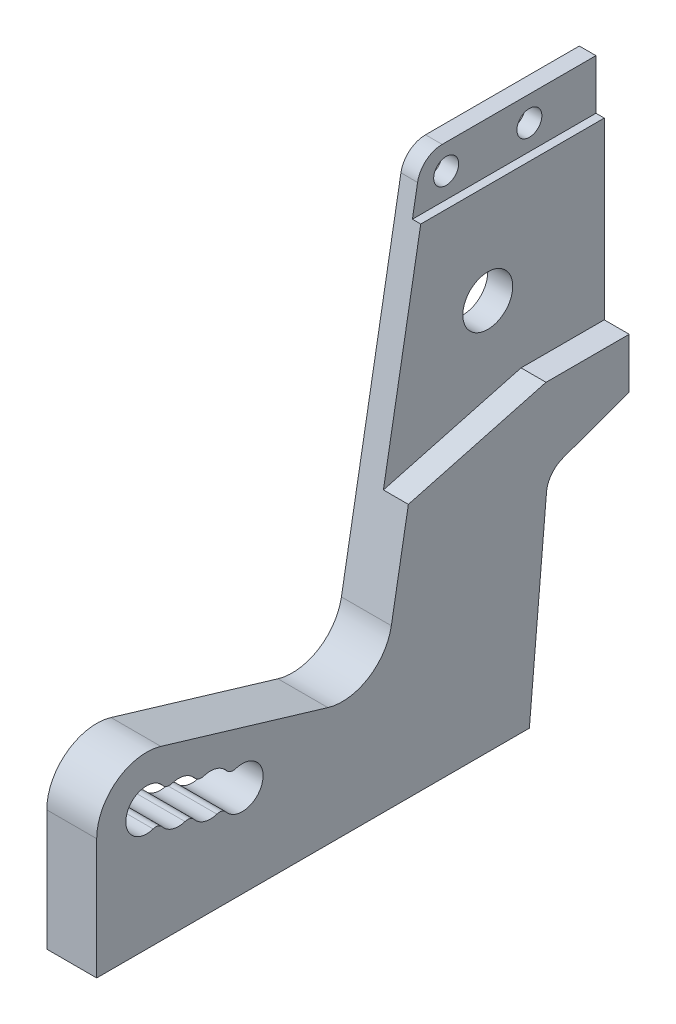
SolidWorks part; units mm, degrees
material "1060 Alloy"
ref_plane "Front Plane" through (0, 0, 0) normal (0, 0, 1) x (1, 0, 0)
ref_plane "Top Plane" through (0, 0, 0) normal (0, 1, 0) x (1, 0, 0)
ref_plane "Right Plane" through (0, 0, 0) normal (1, 0, 0) x (0, 0, -1)
sketch "Sketch1" plane through (0, 0, 0) normal (1, 0, 0) x (0, 0, -1)
  line L1 (0, 0) -> (64, 0)
  line L2 (0, 0) -> (0, 62)
  line L3 (0, 62) -> (64, 62)
  line L4 (64, 0) -> (64, 62)
  circle A0 centre (6, 14.5) radius 2.5
  circle A1 centre (50, 44) radius 3
  dimension "D1" = 6
  dimension "D2" = 5
  dimension "D3" = 14.5
  dimension "D4" = 6
  dimension "D5" = 44
  dimension "D6" = 50
  dimension "D7" = 64
  dimension "D8" = 62
extrude "Boss-Extrude1" add sketch "Sketch1" along normal blind 6
sketch "Sketch3" plane through (6, 0, 0) normal (1, 0, 0) x (0, 0, -1)
  line L57 (64, 0) -> (52, 0)
  line L58 (64, 0) -> (64, 29)
  line L59 (64, 29) -> (54.2259, 25.4425)
  line L60 (52, 0) -> (54.2259, 25.4425)
  dimension "D1" = 70
  dimension "D2" = 29
  dimension "D3" = 52
  dimension "D4" = 85
extrude "Cut-Extrude2" cut sketch "Sketch3" against normal up to next
fillet "Fillet2" radius 3 1 edges at (3, 25.4425, -54.2259)
hole_wizard "Tap Drill for M3 Tap1" positions "Sketch5" profile "Sketch4" hole size "M3" standard "ISO"
sketch "Sketch5" plane through (0, 0, 0) normal (0, -1, 0) x (-1, 0, 0)
  line L0 (0, 0) -> (0, 52) construction
  line L1 (-6, 0) -> (0, 0) construction
  point P0 (-3, 46)
  point P2 (-3, 10)
  dimension "D1" = 3
  dimension "D2" = 10
  dimension "D3" = 36
sketch "Sketch4" plane through (3, 0, -46) normal (1, 0, 0) x (0, 0, -1)
  line L0 (0, 0) -> (0, 9.7511)
  line L1 (0, 9.7511) -> (1.25, 9)
  line L2 (1.25, 9) -> (1.25, 0)
  line L5 (1.25, 0) -> (0, 0)
  line L10 (0, 9.7511) -> (-1.25, 9) construction
  line L11 (0, -6.35) -> (0, 107.95) construction
  dimension "Hole Dia." = 2.5
  dimension "Hole Depth" = 9
  dimension "Drill Angle" = 118
sketch "Sketch9" plane through (6, 0, 0) normal (1, 0, 0) x (0, 0, -1)
  line L0 (7.7183, 20.2487) -> (27.7834, 14.2513)
  line L1 (0, 0) -> (52, 0) construction
  line L19 (43, 62) -> (35.4106, 18.9581)
  line L21 (0, 62) -> (0, 0) construction
  line L22 (43, 62) -> (0, 62)
  line L23 (0, 62) -> (0, 14.5)
  line L24 (0, 62) -> (0, 0) construction
  line L25 (64, 62) -> (0, 62) construction
  arc A0 (35.4106, 18.9581) -> (27.7834, 14.2513) centre (29.5017, 20) cw
  arc A12 (0, 14.5) -> (7.7183, 20.2487) centre (6, 14.5) cw
  circle A16 centre (6, 14.5) radius 2.5 construction
  dimension "D1" = 43
  dimension "D2" = 80
  dimension "D3" = 20
extrude "Cut-Extrude3" cut sketch "Sketch9" against normal blind 8
sketch "Sketch13" plane through (6, 0, 0) normal (1, 0, 0) x (0, 0, -1)
  line L0 (64, 29) -> (64, 62) construction
  line L1 (54, 35) -> (64, 35)
  line L2 (64, 62) -> (43, 62) construction
  line L3 (64, 62) -> (43, 62)
  line L4 (64, 35) -> (64, 62)
  line L5 (35.4106, 18.9581) -> (43, 62) construction
  line L11 (43, 62) -> (37.4576, 30.5675)
  line L15 (37.4576, 30.5675) -> (54, 35)
  dimension "D1" = 10
  dimension "D2" = 65
  dimension "D3" = 27
extrude "Cut-Extrude4" cut sketch "Sketch13" against normal blind 3
fillet "Fillet3" radius 3 1 edges at (1.5, 62, -43)
sketch "Sketch14" plane through (3, 0, 0) normal (1, 0, 0) x (0, 0, -1)
  line L0 (64, 35) -> (64, 62) construction
  line L1 (64, 62) -> (45.5173, 62) construction
  circle A0 centre (56, 59) radius 1.5
  circle A1 centre (46, 59) radius 1.5
  dimension "D1" = 3
  dimension "D2" = 10
  dimension "D3" = 8
  dimension "D4" = 3
extrude "Cut-Extrude5" cut sketch "Sketch14" against normal up to next
sketch "Sketch15" plane through (0, 0, 0) normal (-1, 0, 0) x (0, 0, 1)
  line L0 (-6, 14.5) -> (-26.0652, 8.5026) construction
  line L1 (-27.7834, 14.2513) -> (-7.7183, 20.2487) construction
  circle A0 centre (-9.8325, 13.3545) radius 2.5
  circle A1 centre (-6, 14.5) radius 2.5 construction
  dimension "D1" = 4
extrude "Cut-Extrude6" cut sketch "Sketch15" against normal up to next
pattern_linear "LPattern3" count 3 spacing 4 along (0, -0.2864, -0.9581) of "Cut-Extrude6"
fillet "Fillet4" radius 1 6 edges at (3, 12.4901, -7.4867) (3, 11.3446, -11.3191) (3, 10.1991, -15.1516) (3, 13.0734, -16.0107) (3, 14.2189, -12.1783) (3, 15.3644, -8.3458)
sketch "Sketch16" plane through (3, 0, 0) normal (1, 0, 0) x (0, 0, -1)
  line L0 (42.5629, 59.5209) -> (37.4576, 30.5675) construction
  line L1 (64, 62) -> (41.942, 62)
  line L2 (64, 62) -> (64, 56)
  line L3 (64, 56) -> (41.942, 56)
  line L4 (41.942, 62) -> (41.942, 56)
  dimension "D1" = 6
extrude "Cut-Extrude7" cut sketch "Sketch16" against normal blind 1
